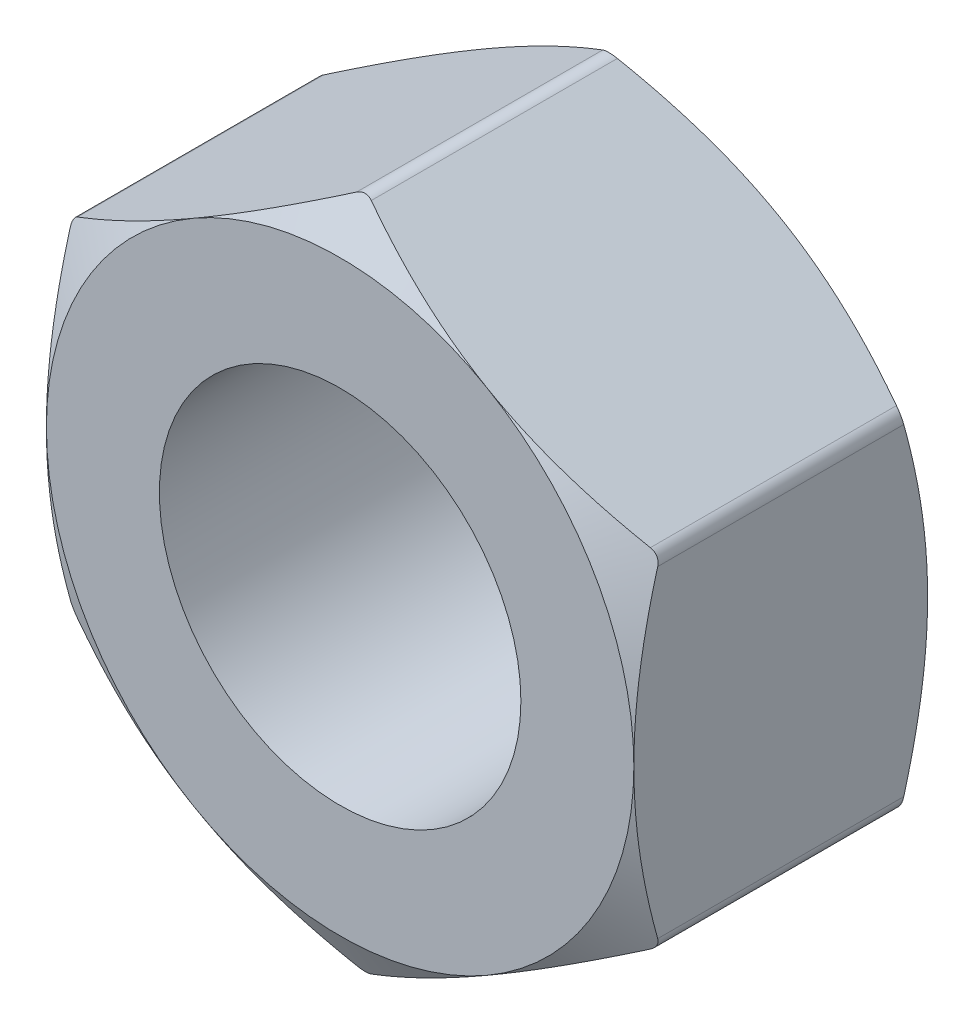
SolidWorks part; units mm, degrees
ref_plane "Front" through (0, 0, 0) normal (0, 0, 1) x (1, 0, 0)
ref_plane "Top" through (0, 0, 0) normal (0, 1, 0) x (1, 0, 0)
ref_plane "Right" through (0, 0, 0) normal (1, 0, 0) x (0, 0, -1)
sketch "Sketch1" plane through (0, 0, 0) normal (0, 0, 1) x (1, 0, 0)
  line L0 (0, 4) -> (0, 2.75) construction
  line L1 (-6.5, 3.7528) -> (-6.5, -3.7528)
  line L2 (-6.5, -3.7528) -> (0, -7.5056)
  line L3 (0, -7.5056) -> (6.5, -3.7528)
  line L4 (6.5, -3.7528) -> (6.5, 3.7528)
  line L5 (6.5, 3.7528) -> (0, 7.5056)
  line L6 (0, 7.5056) -> (-6.5, 3.7528)
  circle A0 centre (0, 0) radius 6.5 construction
  circle A1 centre (0, 0) radius 4 construction
  point P10 (0, 4)
  dimension "Width" = 13
  dimension "Thread Size" = 8
  dimension "Thread Pitch" = 1.25
sketch "Sketch2" plane through (0, 0, 0) normal (1, 0, 0) x (0, 0, -1)
  line L0 (-3.25, 0) -> (3.25, 0) construction
  line L1 (-3.25, 7.5056) -> (3.25, 7.5056) construction
  dimension "Height" = 6.5
sketch "Sketch15" plane through (0, 0, 0) normal (0, 0, 1) x (1, 0, 0)
  line L1 (0, 7.5056) -> (-6.5, 3.7528)
  line L2 (-6.5, 3.7528) -> (-6.5, -3.7528)
  line L3 (-6.5, -3.7528) -> (0, -7.5056)
  line L4 (0, -7.5056) -> (6.5, -3.7528)
  line L5 (6.5, -3.7528) -> (6.5, 3.7528)
  line L6 (6.5, 3.7528) -> (0, 7.5056)
  circle A0 centre (0, 0) radius 6.5 construction
extrude "Boss-Extrude2" add sketch "Sketch15" along normal mid plane 6.5
sketch "Sketch16" plane through (0, 0, 0) normal (0, 0, 1) x (1, 0, 0)
  circle A0 centre (0, 0) radius 4 construction
  circle A1 centre (0, 0) radius 4
sketch "Sketch4" [suppressed] plane through (0, 0, -3.25) normal (0, 0, -1) x (-1, 0, 0)
  circle A0 centre (0, 0) radius 4 construction
  circle A1 centre (0, 0) radius 4
extrude "Cut-Extrude4" cut sketch "Sketch16" against normal through all both and the other way through all
sketch "Sketch7" plane through (0, 0, 3.25) normal (0, 0, 1) x (1, 0, 0)
  circle A0 centre (0, 0) radius 6.5 construction
  circle A1 centre (0, 0) radius 6.5
extrude "Cut-Extrude5" cut sketch "Sketch7" against normal through all draft 60 flip side to cut
mirror "Mirror4" about plane through (0, 0, 0) normal (0, 0, 1) of "Cut-Extrude5"
fillet "Fillet2" radius 0.325 6 edges at (-6.5, 3.7528, 0) (-6.5, -3.7528, 0) (0, -7.5056, 0) (6.5, -3.7528, 0) (6.5, 3.7528, 0) (0, 7.5056, 0)
sketch "Sketch8" plane through (0, 0, 3.25) normal (0, 0, 1) x (1, 0, 0)
  line L0 (1.0353, -3.8637) -> (0, 0) construction
  line L2 (0, 4) -> (0, 2.75) construction
  circle A0 centre (0, 0) radius 4 construction
  point P0 (1.0353, -3.8637)
  dimension "D1" = 15
sketch "Sketch13" [suppressed] plane through (0, 0, -3.25) normal (0, 0, -1) x (-1, 0, 0)
  circle A0 centre (0, 0) radius 4 construction
  circle A1 centre (0, 0) radius 4
extrude "Boss-Extrude1" [suppressed] add sketch "Sketch13" against normal up to surface (6.5 mm away) separate body
curve "Helix/Spiral3" [suppressed] pitch 1.25 height 9 turns 7.2
sketch "Sketch12" [suppressed] plane through (0, 0, 0) normal (1, 0, 0) x (0, 0, -1)
  line L0 (4.3438, 4) -> (3.25, 4)
  line L1 (4.3438, 4) -> (3.875, 3.1881)
  line L2 (3.875, 3.1881) -> (3.7188, 3.1881)
  line L3 (3.7188, 3.1881) -> (3.25, 4)
  line L4 (3.7969, 3.1881) -> (3.7969, 4) construction
  line L5 (3.4844, 3.5941) -> (4.1094, 3.5941) construction
  dimension "D1" = 60
  dimension "D2" = 0.1562
  dimension "D3" = 0.625
sweep "Cut-Sweep1" [suppressed] cut profiles "Sketch12" path "Helix/Spiral3"
sketch "Sketch17" [suppressed] plane through (0, 0, 3.25) normal (0, 0, 1) x (1, 0, 0)
  circle A1 centre (0, 0) radius 4
  circle A2 centre (0, 0) radius 4
  dimension "D1" = 0
extrude "Boss-Extrude3" [suppressed] add sketch "Sketch17" against normal up to surface (6.5 mm away)
combine bodies "Combine1" [suppressed] operation type add bodies to combine 127 118
sketch "Sketch10" [suppressed] plane through (0, 0, 3.25) normal (0, 0, 1) x (1, 0, 0)
  circle A0 centre (0, 0) radius 4 construction
  circle A1 centre (0, 0) radius 4 construction
  circle A2 centre (0, 0) radius 4.125
  dimension "D1" = 0.125
extrude "Cut-Extrude2" [suppressed] cut sketch "Sketch10" against normal through all draft 45
sketch "Sketch11" [suppressed] plane through (0, 0, -3.25) normal (0, 0, -1) x (-1, 0, 0)
  circle A1 centre (0, 0) radius 4.125 construction
  circle A2 centre (0, 0) radius 4.125
extrude "Cut-Extrude3" [suppressed] cut sketch "Sketch11" against normal through all draft 45
equation "\"D1\"= \"Height@Sketch2\""
equation "\"D3@Helix/Spiral3\"=\"Height@Sketch2\"+\"Thread Pitch@Sketch1\"*2"
equation "\"D4@Helix/Spiral3\"=\"Thread Pitch@Sketch1\""
equation "\"D2@Sketch12\" = \"D4@Helix/Spiral3\"*.125"
equation "\"D3@Sketch12\" = \"D4@Helix/Spiral3\"*.50"
equation "\"D1@Boss-Extrude2\"=\"Height@Sketch2\""
equation "\"D1@Fillet2\"=\"Width@Sketch1\"*0.025"
equation "\"D1@Sketch10\"=\"Thread Pitch@Sketch1\"*0.1"
